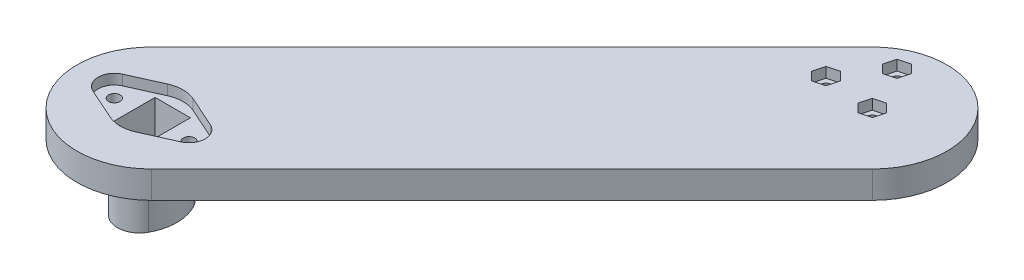
SolidWorks part; units mm, degrees
ref_plane "Front Plane" through (0, 0, 0) normal (0, 0, 1) x (1, 0, 0)
ref_plane "Top Plane" through (0, 0, 0) normal (0, 1, 0) x (1, 0, 0)
ref_plane "Right Plane" through (0, 0, 0) normal (1, 0, 0) x (0, 0, -1)
sketch "Sketch1" plane through (0, 0, 0) normal (0, 1, 0) x (1, 0, 0)
  line L0 (0, 0) -> (106.066, 106.066) construction
  line L25 (-15.5563, 15.5563) -> (90.5097, 121.6224)
  line L26 (15.5563, -15.5563) -> (121.6224, 90.5097)
  line L27 (106.066, 106.066) -> (-1.0853, 181.0942) construction
  line L28 (97.4624, 93.7787) -> (-9.689, 168.8069)
  line L29 (114.6697, 118.3533) -> (7.5183, 193.3815)
  line L30 (99.7189, 119.6662) -> (91.1152, 107.3789) construction
  line L31 (106.9626, 109.4121) -> (103.6165, 108.5155)
  line L32 (103.6165, 108.5155) -> (102.72, 105.1694)
  line L33 (102.72, 105.1694) -> (105.1694, 102.72)
  line L34 (105.1694, 102.72) -> (108.5155, 103.6165)
  line L35 (108.5155, 103.6165) -> (109.4121, 106.9626)
  line L36 (109.4121, 106.9626) -> (106.9626, 109.4121)
  line L37 (97.2329, 93.4511) -> (-9.9184, 168.4793)
  line L38 (90.2186, 104.0328) -> (93.5647, 104.9294)
  line L39 (93.5647, 104.9294) -> (94.4613, 108.2754)
  line L40 (94.4613, 108.2754) -> (92.0118, 110.7249)
  line L41 (92.0118, 110.7249) -> (88.6657, 109.8284)
  line L42 (88.6657, 109.8284) -> (87.7692, 106.4823)
  line L43 (87.7692, 106.4823) -> (90.2186, 104.0328)
  line L44 (100.6154, 123.0122) -> (97.2694, 122.1156)
  line L45 (97.2694, 122.1156) -> (96.3728, 118.7696)
  line L46 (96.3728, 118.7696) -> (98.8223, 116.3201)
  line L47 (98.8223, 116.3201) -> (102.1684, 117.2167)
  line L48 (102.1684, 117.2167) -> (103.0649, 120.5627)
  line L49 (103.0649, 120.5627) -> (100.6154, 123.0122)
  line L66 (114.8991, 118.681) -> (7.7477, 193.7091)
  line L67 (-5.7, 6.7) -> (-5.7, -6.7)
  line L68 (-5.2, 6.2) -> (5.2, 6.2)
  line L69 (-5.2, 6.2) -> (-5.2, -6.2)
  line L70 (-5.2, -6.2) -> (5.2, -6.2)
  line L71 (5.2, 6.2) -> (5.2, -6.2)
  line L72 (-5.7, -6.7) -> (5.7, -6.7)
  line L73 (5.7, 6.7) -> (5.7, -6.7)
  line L74 (-5.7, 6.7) -> (5.7, 6.7)
  line L75 (-11, 0) -> (11, 0) construction
  line L76 (-3.5, 4.5) -> (3.5, 4.5)
  line L77 (3.5, 4.5) -> (3.5, -4.5)
  line L78 (-3.5, -4.5) -> (3.5, -4.5)
  line L79 (-3.5, 4.5) -> (-3.5, -4.5)
  circle A7 centre (0, 0) radius 2.5 construction
  arc A9 (-5.7, 6.7) -> (5.7, 6.7) centre (0, 3.5564) cw
  arc A10 (-5.7, 6.7) -> (-5.7, -6.7) centre (6.4485, 0) ccw
  arc A12 (-15.5563, 15.5563) -> (15.5563, -15.5563) centre (0, 0) ccw
  arc A13 (121.6224, 90.5097) -> (90.5097, 121.6224) centre (106.066, 106.066) ccw
  arc A14 (97.4624, 93.7787) -> (114.6697, 118.3533) centre (106.066, 106.066) ccw
  arc A15 (7.5183, 193.3815) -> (-9.689, 168.8069) centre (-1.0853, 181.0942) ccw
  circle A16 centre (106.066, 106.066) radius 1.7
  circle A17 centre (106.066, 106.066) radius 3 construction
  circle A18 centre (99.7189, 119.6662) radius 1.7
  circle A19 centre (91.1152, 107.3789) radius 1.7
  circle A20 centre (91.1152, 107.3789) radius 3 construction
  circle A21 centre (99.7189, 119.6662) radius 3 construction
  arc A22 (7.7477, 193.7091) -> (-9.9184, 168.4793) centre (-1.0853, 181.0942) ccw
  arc A23 (97.2329, 93.4511) -> (114.8991, 118.681) centre (106.066, 106.066) ccw
  arc A24 (-5.7, -6.7) -> (5.7, -6.7) centre (0, -3.5564) ccw
  arc A25 (5.7, -6.7) -> (5.7, 6.7) centre (-6.4485, 0) ccw
  circle A26 centre (11, 0) radius 1.7
  circle A27 centre (-11, 0) radius 1.7
  point P6 (5.2, 0)
  point P10 (0, 6.2)
  point P14 (53.033, 53.033)
  point P50 (52.4903, 143.5801)
  point P66 (95.417, 113.5225)
  dimension "D4" = 10.4
  dimension "D5" = 5
  dimension "D6" = 1.7
  dimension "D7" = 0.5
  dimension "D8" = 3.4
  dimension "D3" = 12.4
  dimension "D9" = 3.4
  dimension "D10" = 22
  dimension "D13" = 22
  dimension "D17" = 15
  dimension "D18" = 3.4
  dimension "D19" = 6
  dimension "D20" = 3.4
  dimension "D22" = 3.4
  dimension "D23" = 6
  dimension "D24" = 6
  dimension "D14" = 45
  dimension "D15" = 150
  dimension "D16" = 80
  dimension "D21" = 15
  dimension "D25" = 13
  dimension "D26" = 0.4
extrude "Boss-Extrude1" add sketch "Sketch1" along normal blind 8 contours L26 A13 L25 A12
extrude "Boss-Extrude2" add sketch "Sketch1<4>" against normal blind 24.8 from surface contours L74 L67 L72 L73 L68 L71 L70 L69 | A9 L74 | L73 A25 | L72 A24 | L67 A10 starting at face at (53.033, 8, -53.033)
sketch "Sketch1<4>" plane through (0, 0, 0) normal (0, 1, 0) x (1, 0, 0) same geometry as "Sketch1"
extrude "Cut-Extrude3" cut sketch "Sketch1<6>" along normal through all both and the other way through all from offset 5 contours A12 | A12 | L71 L68 L69 L70 | A27 | A26 | A18 | A19 | A16 | L76 L79 L78 L77 region at (0, 0, -6.0382) region at (0, 0, 0) region at (106.066, 0, -106.066) region at (99.7189, 0, -119.6662) region at (91.1152, 0, -107.3789) region at (11, 0, 0) region at (-11, 0, 0) offset against normal yes
sketch "Sketch1<6>" plane through (0, 0, 0) normal (0, 1, 0) x (1, 0, 0) same geometry as "Sketch1"
extrude "Boss-Extrude3" add sketch "Sketch1<10>" against normal blind 0.7 from surface contours L74 L67 L72 L73 L68 L71 L70 L69 | L71 L68 L69 L70 | A9 L74 | L73 A25 | L72 A24 | L67 A10 region at (0, 0, -6.5241) region at (0, 0, -8.0815) region at (-6.3938, 0, 0) region at (0, 0, 8.0815) region at (6.3938, 0, 0) region at (0, 0, -6.0382) starting at face at (0, -16.8, 0)
sketch "Sketch1<10>" plane through (0, 0, 0) normal (0, 1, 0) x (1, 0, 0) same geometry as "Sketch1"
sketch "Sketch2" plane through (0, 8, 0) normal (0, 1, 0) x (1, 0, 0)
  line L0 (-3.7841, 8.4406) -> (-12.9432, 4.3343)
  line L1 (-12.9432, -4.3343) -> (-3.7841, -8.4406)
  line L2 (12.9432, -4.3343) -> (3.7841, -8.4406)
  line L3 (12.9432, 4.3343) -> (3.7841, 8.4406)
  line L4 (-11, 0) -> (11, 0) construction
  circle A0 centre (0, 0) radius 9.25
  circle A1 centre (11, 0) radius 4.75
  circle A2 centre (-11, 0) radius 4.75
  dimension "D1" = 9.5
  dimension "D2" = 9.5
  dimension "D3" = 18.5
  dimension "D4" = 22
extrude "Cut-Extrude7" cut sketch "Sketch2" against normal blind 3 contours A2 A0 L0 | A2 L1 A0 | A1 A0 L2 | A1 L3 A0 | A2 | A0 | A1 region at (-8.5208, 8, -5.6136) region at (8.5208, 8, -5.6136) region at (-8.5208, 8, 5.6136) region at (8.5208, 8, 5.6136)
extrude "Cut-Extrude5" cut sketch "Sketch1<8>" against normal blind 3 from surface contours L48 L49 L44 L45 L46 L47 A18 | L42 L43 L38 L39 L40 L41 A19 | L35 L36 L31 L32 L33 L34 A16 region at (108.1204, 0, -108.1204) region at (89.0608, 0, -105.3245) region at (101.7733, 0, -121.7206) starting at face at (0, 8, 0)
sketch "Sketch1<8>" plane through (0, 0, 0) normal (0, 1, 0) x (1, 0, 0) same geometry as "Sketch1"
extrude "Cut-Extrude6" cut sketch "Sketch1<9>" along normal blind 3 from surface contours L66 A22 L37 A23 starting at face at (-11, 0, 1.7)
sketch "Sketch1<9>" plane through (0, 0, 0) normal (0, 1, 0) x (1, 0, 0) same geometry as "Sketch1"
